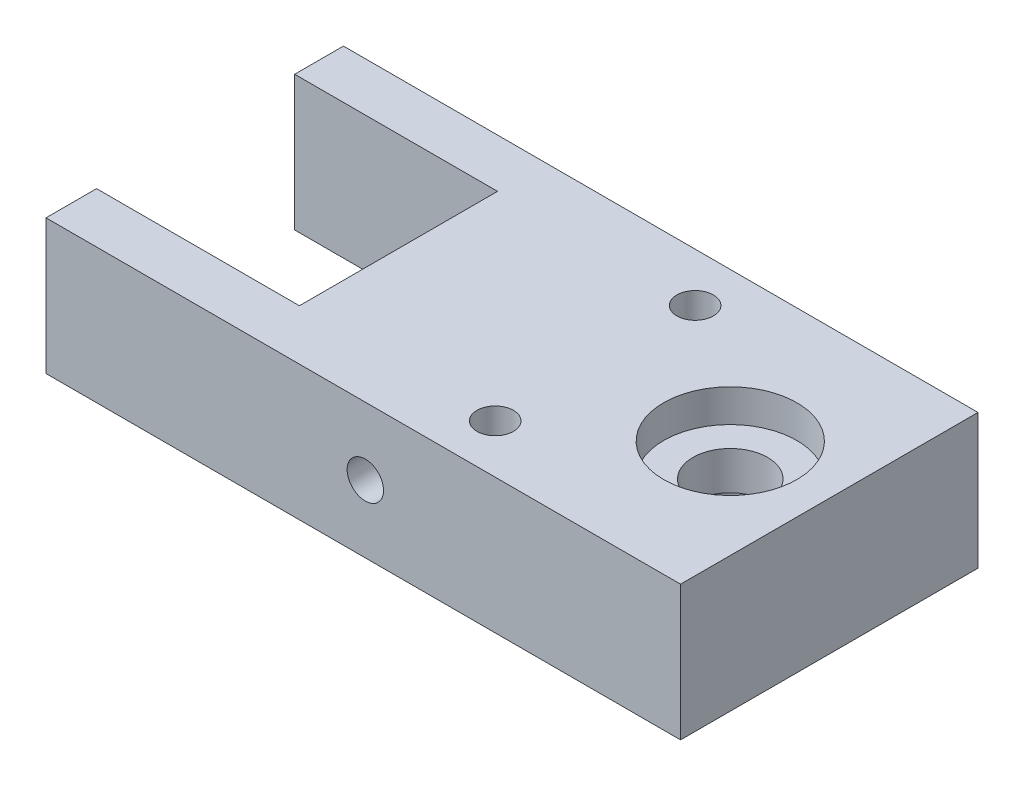
SolidWorks part; units mm, degrees
material "1060 Alloy"
ref_plane "Front Plane" through (0, 0, 0) normal (0, 0, 1) x (1, 0, 0)
ref_plane "Top Plane" through (0, 0, 0) normal (0, 1, 0) x (1, 0, 0)
ref_plane "Right Plane" through (0, 0, 0) normal (1, 0, 0) x (0, 0, -1)
sketch "Sketch1" plane through (0, 0, 0) normal (0, 1, 0) x (1, 0, 0)
  line L0 (0, 0) -> (-31.72, 0) construction
  line L1 (0, 0) -> (0, 18.4405) construction
  line L2 (-31.72, 9.53) -> (-31.72, -9.36)
  line L3 (-31.72, -9.36) -> (-51.06, -9.36)
  line L4 (-51.06, -9.36) -> (-51.06, -14.18)
  line L5 (-51.06, -14.18) -> (9.44, -14.18)
  line L6 (9.44, -14.18) -> (9.44, 14.18)
  line L7 (9.44, 14.18) -> (-51.06, 14.18)
  line L8 (-51.06, 14.18) -> (-51.06, 9.53)
  line L9 (-51.06, 9.53) -> (-31.72, 9.53)
  line L10 (-31.72, -9.46) -> (-31.72, 9) construction
  circle A0 centre (0, 0) radius 3.56
  circle A1 centre (0, 0) radius 8.474 construction
  dimension "D1" = 7.12
  dimension "D2" = 60.5
  dimension "D3" = 28.36
  dimension "D4" = 4.82
  dimension "D5" = 41.16
  dimension "D6" = 4.65
extrude "Boss-Extrude1" add sketch "Sketch1" along normal blind 12.86
sketch "Sketch2" plane through (-31.72, 0, 0) normal (-1, 0, 0) x (0, 0, 1)
  line L0 (-0.085, 6.43) -> (-0.085, 0) construction
  line L1 (-9.53, 0) -> (9.36, 0) construction
  line L2 (-0.085, 6.43) -> (-9.53, 6.43) construction
  line L3 (-9.53, 12.86) -> (-9.53, 0) construction
  circle A0 centre (-0.085, 6.43) radius 2.085
  dimension "D1" = 4.17
extrude "Cut-Extrude1" cut sketch "Sketch2" against normal blind 12.7
sketch "Sketch3" plane through (0, 12.86, 0) normal (0, 1, 0) x (-1, 0, 0)
  circle A0 centre (0, 0) radius 6.35
  dimension "D1" = 12.7
extrude "Cut-Extrude2" cut sketch "Sketch3" against normal blind 3.12
sketch "Sketch4" plane through (0, 0, 0) normal (0, -1, 0) x (1, 0, 0)
  circle A0 centre (0, 0) radius 5.57
  dimension "D1" = 11.14
extrude "Cut-Extrude3" cut sketch "Sketch4" against normal blind 6.08
sketch "Sketch5" plane through (0, 0, 0) normal (0, -1, 0) x (1, 0, 0)
  line L0 (-12.88, 9.53) -> (-12.88, -9.53) construction
  line L1 (0, 0) -> (-12.3777, 0) construction
  line L2 (-12.88, 7.79) -> (-4.8481, 7.79) construction
  line L3 (-12.88, -7.79) -> (-4.8481, -7.79) construction
  line L4 (-11.14, 9.53) -> (-11.14, -9.53) construction
  line L5 (9.44, 14.18) -> (9.44, -14.18) construction
  circle A0 centre (-12.88, -9.53) radius 1.74
  circle A1 centre (-12.88, 9.53) radius 1.74
  dimension "D2" = 3.48
  dimension "D1" = 15.58
  dimension "D3" = 20.58
extrude "Cut-Extrude4" cut sketch "Sketch5" against normal through all
sketch "Sketch6" plane through (0, 0, 14.18) normal (0, 0, 1) x (1, 0, 0)
  line L0 (9.44, 6.43) -> (-20.615, 6.43) construction
  line L1 (9.44, 12.86) -> (9.44, 0) construction
  line L2 (-18.88, 6.43) -> (-18.88, 0) construction
  line L3 (-51.06, 0) -> (9.44, 0) construction
  circle A0 centre (-20.615, 6.43) radius 1.735
  dimension "D2" = 3.47
  dimension "D1" = 28.32
extrude "Cut-Extrude5" cut sketch "Sketch6" against normal blind 5
